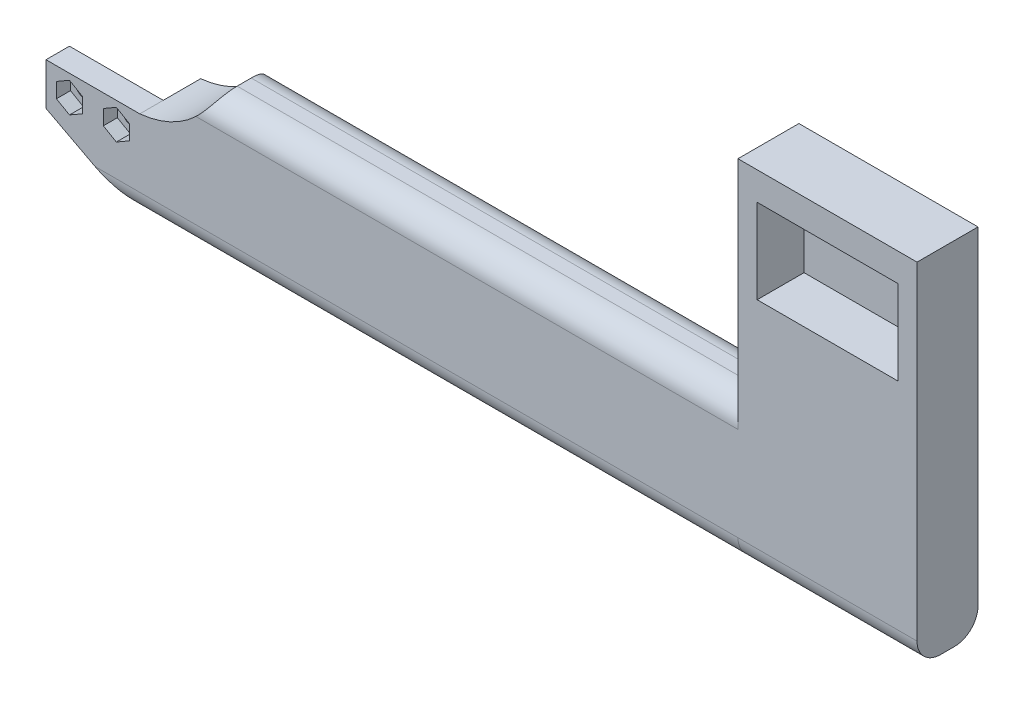
SolidWorks part; units mm, degrees
ref_plane "Front Plane" through (0, 0, 0) normal (0, 0, 1) x (1, 0, 0)
ref_plane "Top Plane" through (0, 0, 0) normal (0, 1, 0) x (1, 0, 0)
ref_plane "Right Plane" through (0, 0, 0) normal (1, 0, 0) x (0, 0, -1)
sketch "Sketch1" plane through (0, 0, 0) normal (0, 0, 1) x (1, 0, 0)
  line L0 (23.1362, 112.1119) -> (3.1362, 112.1119)
  line L1 (23.1362, 116.6119) -> (23.1362, 107.6119)
  line L2 (23.1362, 116.6119) -> (3.1362, 116.6119)
  line L3 (3.1362, 116.6119) -> (3.1362, 107.6119)
  line L4 (23.1362, 107.6119) -> (3.1362, 107.6119)
  line L5 (8.1362, 108.9076) -> (10.9112, 110.5097)
  line L6 (10.9112, 110.5097) -> (10.9112, 113.714)
  line L7 (10.9112, 113.714) -> (8.1362, 115.3162)
  line L8 (8.1362, 115.3162) -> (5.3612, 113.714)
  line L9 (5.3612, 113.714) -> (5.3612, 110.5097)
  line L10 (5.3612, 110.5097) -> (8.1362, 108.9076)
  line L11 (18.1362, 108.9076) -> (20.9112, 110.5097)
  line L12 (20.9112, 110.5097) -> (20.9112, 113.714)
  line L13 (20.9112, 113.714) -> (18.1362, 115.3162)
  line L14 (18.1362, 115.3162) -> (15.3612, 113.714)
  line L15 (15.3612, 113.714) -> (15.3612, 110.5097)
  line L16 (15.3612, 110.5097) -> (18.1362, 108.9076)
  circle A0 centre (8.1362, 112.1119) radius 2.775 construction
  circle A1 centre (18.1362, 112.1119) radius 2.775 construction
  circle A2 centre (18.1362, 112.1119) radius 1.5
  circle A3 centre (8.1362, 112.1119) radius 1.5
  point P24 (0, 0)
  point P26 (7.9219, 112.1119)
  dimension "D3" = 3
  dimension "D4" = 3
  dimension "D1" = 5.55
  dimension "D2" = 5.55
  dimension "D5" = 0
  dimension "D6" = 0
extrude "Boss-Extrude1" add sketch "Sketch1" along normal blind 5 contours L15 L14 L13 L12 L0 L1 L2 L3 L9 L8 L7 L6 | L16 L15 L0 L6 L5 L10 L9 L3 L4 L1 L12 L11 region at (13.1362, 109.439, 0) region at (13.1362, 114.7848, 0)
extrude "Boss-Extrude2" add sketch "Sketch1<4>" along normal blind 2 contours A3 L0 L6 L7 L8 L9 | A3 L0 L9 L10 L5 L6 | A2 L0 L12 L13 L14 L15 | A2 L0 L15 L16 L11 L12 region at (20.8471, 111.3108, 0) region at (20.2737, 112.1759, 0) region at (5.4253, 112.9129, 0) region at (5.9987, 112.0478, 0)
sketch "Sketch1<4>" plane through (0, 0, 0) normal (0, 0, 1) x (1, 0, 0) same geometry as "Sketch1"
sketch "Sketch2" plane through (0, 0, 5) normal (0, 0, 1) x (1, 0, 0)
  line L0 (3.1362, 107.6119) -> (23.1362, 97.1119)
  line L5 (3.1362, 112.1119) -> (13.404, 112.1119)
  line L6 (3.1362, 116.6119) -> (3.1362, 107.6119) construction
  line L7 (188.9008, 127.1119) -> (38.9008, 127.1119)
  line L8 (188.9008, 127.1119) -> (188.9008, 97.1119)
  line L9 (188.9008, 97.1119) -> (23.1362, 97.1119)
  line L11 (3.1362, 107.6119) -> (23.1362, 107.6119)
  line L13 (23.1362, 107.6119) -> (23.1362, 116.6119)
  arc A0 (23.1362, 116.6119) -> (38.9008, 127.1119) centre (21.1784, 136.6357) ccw
  point P5 (113.9008, 127.1119)
  line M9 (23.1362, 107.6119) -> (23.1362, 116.6119)
  dimension "D1" = 30
  dimension "D2" = 150
extrude "Boss-Extrude3" add sketch "Sketch2" against normal blind 13 contours L7 L9 L8 M9 region at (105.8729, 111.6963, 5)
fillet "Fillet2" radius 5 4 edges at (113.9008, 127.1119, -8) (106.0185, 97.1119, -8) (113.9008, 127.1119, 5) (106.0185, 97.1119, 5)
sketch "Sketch6" plane through (0, 0, 5) normal (0, 0, 1) x (1, 0, 0)
  line L0 (188.9008, 112.1119) -> (170.9008, 112.1119)
  line L1 (155.9008, 121.1119) -> (185.9008, 121.1119)
  line L2 (155.9008, 121.1119) -> (155.9008, 103.1119)
  line L3 (155.9008, 103.1119) -> (185.9008, 103.1119)
  line L4 (185.9008, 121.1119) -> (185.9008, 103.1119)
  line L5 (155.9008, 121.1119) -> (185.9008, 103.1119) construction
  line L6 (155.9008, 103.1119) -> (185.9008, 121.1119) construction
  line L8 (188.9008, 122.1119) -> (188.9008, 102.1119) construction
  dimension "D1" = 18
extrude "Cut-Extrude1" cut sketch "Sketch6" against normal blind 9.5 contours L4 L1 L2 L3 region at (170.9008, 120.762, 5)
sketch "Sketch7" plane through (0, 0, -8) normal (0, 0, -1) x (-1, 0, 0)
  line L0 (-188.9008, 112.1119) -> (-188.9008, 157.1119)
  line L1 (-188.9008, 122.1119) -> (-188.9008, 102.1119) construction
  line L4 (-154.8042, 166.1119) -> (-184.8042, 166.1119)
  line L5 (-154.8042, 166.1119) -> (-154.8042, 148.1119)
  line L6 (-154.8042, 148.1119) -> (-184.8042, 148.1119)
  line L7 (-184.8042, 166.1119) -> (-184.8042, 148.1119)
  line L8 (-154.8042, 166.1119) -> (-184.8042, 148.1119) construction
  line L9 (-154.8042, 148.1119) -> (-184.8042, 166.1119) construction
  line L12 (-150.7076, 172.1119) -> (-188.9008, 172.1119)
  line L13 (-150.7076, 172.1119) -> (-150.7076, 97.1119)
  line L14 (-150.7076, 97.1119) -> (-188.9008, 97.1119)
  line L15 (-188.9008, 172.1119) -> (-188.9008, 97.1119)
  line L16 (-150.7076, 172.1119) -> (-188.9008, 97.1119) construction
  line L17 (-150.7076, 97.1119) -> (-188.9008, 172.1119) construction
  point P4 (-169.8042, 157.1119)
  point P12 (-169.8042, 134.6119)
  line M11 (-35.1013, 122.1119) -> (-188.9008, 122.1119)
  line M12 (-188.9008, 122.1119) -> (-188.9008, 102.1119)
  line M13 (-188.9008, 102.1119) -> (-13.6124, 102.1119)
  dimension "D2" = 18
  dimension "D3" = 30
extrude "Boss-Extrude7" add sketch "Sketch7" against normal blind 13 contours L12 L15 L0 L13 L7 L4 L5 L6 M11 | L15 L14 L13 M13 | L13 M11 M12 M13 region at (169.8042, 112.1119, -8) region at (169.8042, 143.1693, -8) region at (169.8042, 99.6119, -8)
fillet "Fillet3" radius 5 1 edges at (169.8042, 97.1119, 5)
fillet "Fillet4" radius 5 1 edges at (169.8042, 97.1119, -8)
extrude "Boss-Extrude8" add sketch "Sketch7<3>" against normal blind 3 contours L4 L7 L6 L5 region at (169.8042, 157.1119, -8)
sketch "Sketch7<3>" plane through (0, 0, -8) normal (0, 0, -1) x (-1, 0, 0) same geometry as "Sketch7"
